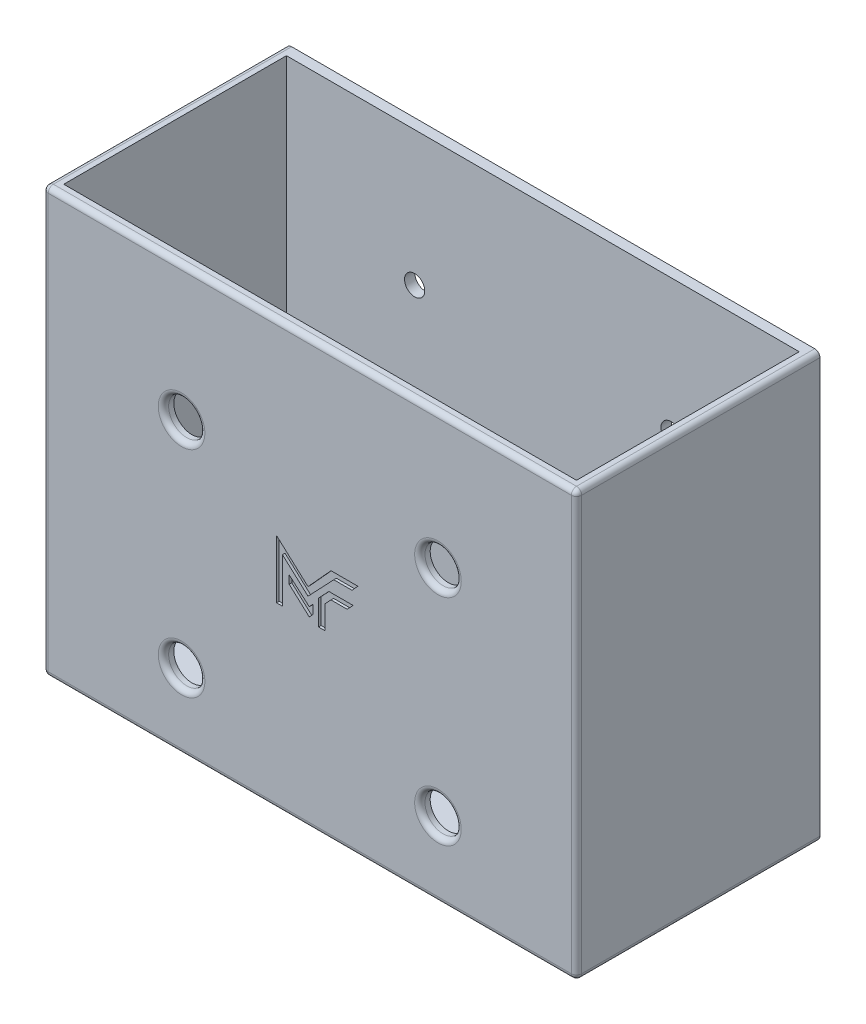
SolidWorks part; units mm, degrees
ref_plane "Plano frontal" through (0, 0, 0) normal (0, 0, 1) x (1, 0, 0)
ref_plane "Plano superior" through (0, 0, 0) normal (0, 1, 0) x (1, 0, 0)
ref_plane "Plano direito" through (0, 0, 0) normal (1, 0, 0) x (0, 0, -1)
sketch "Esboço1" plane through (0, 0, 0) normal (0, 1, 0) x (1, 0, 0)
  line L0 (-51.5, 0) -> (51.5, 0)
  line L1 (51.5, 0) -> (51.5, 47)
  line L2 (51.5, 47) -> (-51.5, 47)
  line L3 (-51.5, 47) -> (-51.5, 0)
  point P4 (0, 0)
  dimension "D1" = 103
  dimension "D2" = 47
extrude "Ressalto-extrusão1" add sketch "Esboço1" against normal blind 2
sketch "Esboço2" plane through (0, 0, 0) normal (0, 1, 0) x (1, 0, 0)
  line L0 (51.5, 47) -> (-51.5, 47) construction
  line L1 (51.5, 47) -> (-51.5, 47)
  line L2 (-51.5, 47) -> (-51.5, 0) construction
  line L3 (-51.5, 47) -> (-51.5, 0)
  line L4 (51.5, 0) -> (51.5, 47) construction
  line L5 (-51.5, 0) -> (51.5, 0) construction
  line L6 (51.5, 0) -> (51.5, 47)
  line L7 (-51.5, 0) -> (51.5, 0)
  line L8 (49.5, 45) -> (-49.5, 45)
  line L9 (-49.5, 45) -> (-49.5, 2)
  line L10 (-49.5, 2) -> (49.5, 2)
  line L11 (49.5, 2) -> (49.5, 45)
  dimension "D1" = 2
extrude "Ressalto-extrusão2" add sketch "Esboço2" along normal blind 80
sketch "Esboço3" plane through (0, 0, -45) normal (0, 0, 1) x (1, 0, 0)
  line L0 (-49.5, 28) -> (49.5, 28)
  line L1 (-49.5, 80) -> (-49.5, 0) construction
  line L2 (49.5, 80) -> (49.5, 0) construction
  line L3 (49.5, 0) -> (-49.5, 0) construction
  line L4 (-49.5, 25) -> (49.5, 25)
  line L5 (-49.5, 28) -> (-49.5, 25)
  line L6 (49.5, 28) -> (49.5, 25)
  dimension "D1" = 28
  dimension "D2" = 3
extrude "Ressalto-extrusão3" add sketch "Esboço3" along normal blind 3
fillet "Filete1" radius 5 1 edges at (0, 25, -45)
sketch "Esboço4" plane through (0, 0, -45) normal (0, 0, 1) x (1, 0, 0)
  line L0 (0, 25) -> (0, 0) construction
  line L1 (-49.5, 25) -> (49.5, 25) construction
  line L2 (0, 12.5) -> (49.5, 12.5) construction
  line L3 (49.5, 20.4174) -> (49.5, 0) construction
  line L4 (0, 28) -> (0, 80) construction
  line L5 (49.5, 28) -> (-49.5, 28) construction
  line L6 (49.5, 80) -> (-49.5, 80) construction
  line L7 (0, 54) -> (49.5, 54) construction
  line L8 (49.5, 20.4174) -> (-49.5, 20.4174) construction
  circle A0 centre (24.75, 12.5) radius 1.95
  circle A1 centre (24.75, 54) radius 1.95
  circle A2 centre (-24.75, 12.5) radius 1.95
  circle A3 centre (-24.75, 54) radius 1.95
  dimension "D1" = 3.9
  dimension "D2" = 24.75
extrude "Corte-extrusão1" cut sketch "Esboço4" against normal blind 3
sketch "Esboço5" plane through (0, 0, 0) normal (0, 0, 1) x (1, 0, 0)
  circle A0 centre (-24.75, 54) radius 3.5
  circle A1 centre (24.75, 54) radius 3.5
  circle A2 centre (-24.75, 12.5) radius 3.5
  circle A3 centre (24.75, 12.5) radius 3.5
  dimension "D1" = 7
extrude "Corte-extrusão2" cut sketch "Esboço5" against normal blind 3
fillet "Filete2" radius 1 4 edges at (28.25, 12.5, 0) (-21.25, 12.5, 0) (28.25, 54, 0) (-21.25, 54, 0)
fillet "Filete3" radius 1 8 edges at (-51.5, 80, -23.5) (0, 80, 0) (51.5, 80, -23.5) (51.5, -2, -23.5) (0, -2, 0) (-51.5, -2, -23.5) (-51.5, 39, 0) (51.5, 39, 0)
sketch "Esboço6" plane through (0, -2, 0) normal (0, -1, 0) x (1, 0, 0)
  line L0 (0, 0) -> (0, -47) construction
  line L1 (50.5, -47) -> (-50.5, -47) construction
  line L2 (0, -23.5) -> (51.5, -23.5) construction
  line L3 (51.5, -1) -> (51.5, -47) construction
  line L4 (21.75, -23.5) -> (29.75, -23.5) construction
  line L5 (21.75, -17.5) -> (29.75, -17.5)
  line L6 (21.75, -29.5) -> (29.75, -29.5)
  line L7 (-21.75, -23.5) -> (-29.75, -23.5) construction
  line L8 (-21.75, -17.5) -> (-29.75, -17.5)
  line L9 (-21.75, -29.5) -> (-29.75, -29.5)
  arc A0 (21.75, -17.5) -> (21.75, -29.5) centre (21.75, -23.5) ccw
  arc A1 (29.75, -29.5) -> (29.75, -17.5) centre (29.75, -23.5) ccw
  arc A2 (-21.75, -17.5) -> (-21.75, -29.5) centre (-21.75, -23.5) cw
  arc A3 (-29.75, -29.5) -> (-29.75, -17.5) centre (-29.75, -23.5) cw
  point P11 (25.75, -23.5)
  point P19 (-25.75, -23.5)
  point P24 (25.75, -23.5)
  dimension "D1" = 6
  dimension "D3" = 8
extrude "Corte-extrusão3" cut sketch "Esboço6" against normal blind 3
fillet "Filete4" radius 1 16 edges at (25.75, -2, -17.5) (35.75, -2, -23.5) (25.75, -2, -29.5) (-25.75, -2, -17.5) (-15.75, -2, -23.5) (-25.75, -2, -29.5) (15.75, -2, -23.5) (-35.75, -2, -23.5) (15.75, 0, -23.5) (25.75, 0, -29.5) (35.75, 0, -23.5) (-35.75, 0, -23.5) (-25.75, 0, -29.5) (-15.75, 0, -23.5) (25.75, 0, -17.5) (-25.75, 0, -17.5)
sketch "Esboço7" plane through (0, -2, 0) normal (0, -1, 0) x (1, 0, 0)
  line L0 (0, -12.5) -> (51.5, -12.5) construction
  line L4 (0, 0) -> (0, -47) construction
  line L5 (50.5, -47) -> (-50.5, -47) construction
  line L6 (51.5, -1) -> (51.5, -47) construction
  line L7 (0, -12.5) -> (-51.5, -12.5) construction
  line L8 (-51.5, -47) -> (-51.5, -1) construction
  line L9 (29.75, -17.5) -> (21.75, -17.5) construction
  text T0 "<b> AC</b>"
  text T1 "<b>DC</b>"
  dimension "D1" = 5
extrude "Corte-extrusão4" cut sketch "Esboço7" against normal blind 0.5
sketch "Logo_MF" plane through (0, 0, 0) normal (0, 0, 1) x (1, 0, 0)
  line L0 (-6.4127, 32.5654) -> (-5.2791, 32.5654)
  line L1 (-5.2791, 32.5654) -> (-5.2791, 41.1853)
  line L2 (-5.2791, 41.1853) -> (-0.3401, 36.6988)
  line L3 (-0.3401, 36.6988) -> (4.643, 41.9417)
  line L4 (4.643, 41.9417) -> (8.1619, 41.9417)
  line L5 (8.1619, 41.9417) -> (9.2898, 43.1834)
  line L6 (9.2898, 43.1834) -> (4.0993, 43.1834)
  line L7 (4.0993, 43.1834) -> (-0.3383, 38.2983)
  line L8 (-0.3383, 38.2983) -> (-6.4127, 43.8161)
  line L9 (-6.4127, 43.8161) -> (-6.4127, 32.5654)
  line L10 (-3.9704, 38.4461) -> (-3.9704, 36.8756)
  line L11 (-3.9704, 36.8756) -> (-0.09, 33.3507)
  line L12 (-0.09, 33.3507) -> (0.5909, 34.1003)
  line L13 (0.5909, 34.1003) -> (0.5909, 35.8204)
  line L14 (0.5909, 35.8204) -> (-0.0911, 35.0696)
  line L15 (-0.0911, 35.0696) -> (-3.9704, 38.4461)
  line L16 (1.6909, 32.5654) -> (1.6909, 37.4075)
  line L17 (1.6909, 37.4075) -> (3.6909, 39.5117)
  line L18 (3.6909, 39.5117) -> (8.3744, 39.5117)
  line L19 (8.3744, 39.5117) -> (7.222, 38.2992)
  line L20 (7.222, 38.2992) -> (4.0998, 38.2992)
  line L21 (4.0998, 38.2992) -> (2.906, 37.0431)
  line L22 (2.906, 37.0431) -> (2.906, 32.5654)
  line L23 (2.906, 32.5654) -> (1.6909, 32.5654)
  line L24 (50.5, -1) -> (50.5, 79) construction
  line L25 (50.5, 79) -> (-50.5, 79) construction
  dimension "D1" = 2.43
  dimension "D2" = 6.97
  dimension "D3" = 1.1
  dimension "D4" = 41.2102
  dimension "D5" = 42.1256
  dimension "D6" = 42.3381
  dimension "D7" = 43.278
  dimension "D8" = 45.857
  dimension "D9" = 46.4002
  dimension "D10" = 46.4007
  dimension "D11" = 46.8091
  dimension "D12" = 47.594
  dimension "D13" = 48.8091
  dimension "D14" = 54.4704
  dimension "D15" = 50.59
  dimension "D16" = 50.5911
  dimension "D17" = 50.8383
  dimension "D18" = 50.8401
  dimension "D19" = 56.9127
  dimension "D20" = 35.1839
  dimension "D21" = 35.8166
  dimension "D22" = 37.8147
  dimension "D23" = 40.5539
  dimension "D24" = 42.1244
  dimension "D25" = 43.1796
  dimension "D26" = 46.4346
extrude "Corte-extrusão5" cut sketch "Logo_MF" against normal blind 0.5
